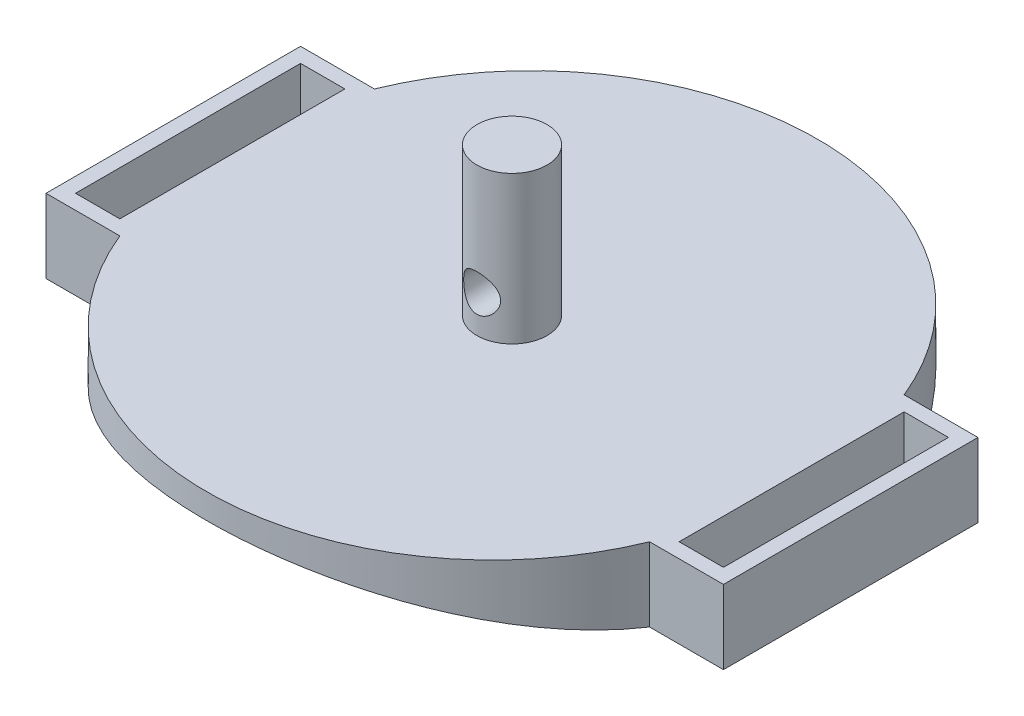
SolidWorks part; units mm, degrees
ref_plane "Front Plane" through (0, 0, 0) normal (0, 0, 1) x (1, 0, 0)
ref_plane "Top Plane" through (0, 0, 0) normal (0, 1, 0) x (1, 0, 0)
ref_plane "Right Plane" through (0, 0, 0) normal (1, 0, 0) x (0, 0, -1)
sketch "Sketch4" plane through (0, 0, 0) normal (0, 1, 0) x (1, 0, 0)
  line L1 (0, -55) -> (0, 55) construction
  line L3 (-52.8407, -31.5076) -> (52.8407, -31.5076) construction
  line L4 (0, 9.8422) -> (0, -72.8575) construction
  line L6 (35.8579, -48.7381) -> (45.8579, -48.7381)
  line L7 (35.8579, -14.2772) -> (45.8579, -14.2772)
  line L8 (45.8579, -48.7381) -> (45.8579, -14.2772)
  line L9 (-35.8579, -14.2772) -> (-45.8579, -14.2772)
  line L10 (-45.8579, -48.7381) -> (-45.8579, -14.2772)
  line L11 (-35.8579, -48.7381) -> (-45.8579, -48.7381)
  line L12 (-35.8579, -48.7381) -> (-35.8579, -14.2772) construction
  line L13 (37.8579, -46.7381) -> (37.8579, -16.2772)
  line L14 (-43.8579, -46.7381) -> (-37.8579, -46.7381)
  line L15 (-43.8579, -46.7381) -> (-43.8579, -16.2772)
  line L16 (-43.8579, -16.2772) -> (-37.8579, -16.2772)
  line L17 (-37.8579, -46.7381) -> (-37.8579, -16.2772)
  line L18 (43.8579, -16.2772) -> (37.8579, -16.2772)
  line L19 (43.8579, -46.7381) -> (43.8579, -16.2772)
  line L20 (43.8579, -46.7381) -> (37.8579, -46.7381)
  arc A1 (-35.8579, -48.7381) -> (35.8579, -48.7381) centre (0, -34.143) ccw
  arc A2 (-35.8579, -14.2772) -> (35.8579, -14.2772) centre (0, -28.8723) cw
  dimension "D2" = 34.461
  dimension "D3" = 2
  dimension "D1" = 2
  dimension "D4" = 2
  dimension "D5" = 10
  dimension "D6" = 2
  dimension "D7" = 10
extrude "Boss-Extrude3" add sketch "Sketch4" along normal blind 10
sketch "Sketch5" plane through (0, 10, 0) normal (0, 1, 0) x (1, 0, 0)
  line L0 (0, 9.8422) -> (0, -72.8575) construction
  line L1 (-52.8407, -44.8867) -> (52.8407, -44.8867) construction
  line L2 (-52.8407, -27.6562) -> (-52.8407, -62.1172) construction
  line L3 (52.8407, -62.1172) -> (52.8407, -27.6562) construction
  arc A0 (35.8579, -14.2772) -> (-35.8579, -14.2772) centre (0, -28.8723) ccw construction
  arc A1 (-35.8579, -48.7381) -> (35.8579, -48.7381) centre (0, -34.143) ccw construction
  circle A2 centre (0, -31.5076) radius 4.75
  dimension "D1" = 9.5
extrude "Boss-Extrude4" add sketch "Sketch5" along normal blind 20
ref_plane "Plane1" through (0, 0, 26.7576) normal (0, 0, -1) x (-1, 0, 0)
sketch "Sketch6" plane through (0, 0, 26.7576) normal (0, 0, -1) x (-1, 0, 0)
  line L0 (35.8579, 10) -> (-35.8579, 10) construction
  circle A0 centre (0, 15) radius 2.5
  dimension "D1" = 5
  dimension "D2" = 5
extrude "Cut-Extrude1" cut sketch "Sketch6" against normal up to next
ref_plane "Plane2" through (0, 0, 72.8575) normal (0, 0, 1) x (1, 0, 0)
sketch "Sketch7" plane through (0, 0, 72.8575) normal (0, 0, 1) x (1, 0, 0)
  line L0 (-35.8579, 0) -> (35.8579, 0)
  arc A0 (-35.8579, 0) -> (35.8579, 0) centre (0, -94.0088) cw
extrude "Cut-Extrude2" cut sketch "Sketch7" against normal up to next
